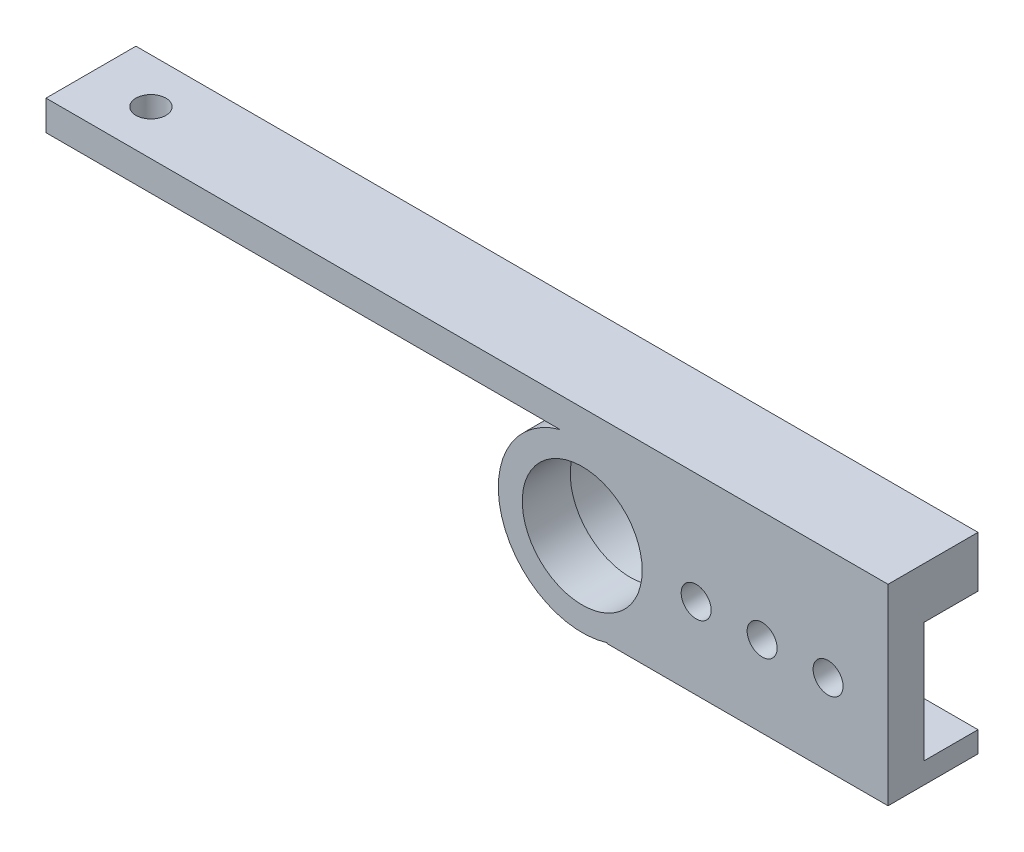
SolidWorks part; units mm, degrees
ref_plane "前视基准面" through (0, 0, 0) normal (0, 0, 1) x (1, 0, 0)
ref_plane "上视基准面" through (0, 0, 0) normal (0, 1, 0) x (1, 0, 0)
ref_plane "右视基准面" through (0, 0, 0) normal (1, 0, 0) x (0, 0, -1)
sketch "草图1" plane through (0, 0, 0) normal (0, 0, 1) x (1, 0, 0)
  line L1 (20, -10) -> (-20, -10)
  line L2 (20, -10) -> (20, 10)
  line L3 (20, 10) -> (-20, 10)
  line L4 (-20, -10) -> (-20, 10)
  line L5 (20, -10) -> (-20, 10) construction
  line L6 (20, 10) -> (-20, -10) construction
  point P0 (0, 0)
  dimension "D1" = 40
  dimension "D2" = 20
extrude "凸台-拉伸1" add sketch "草图1" along normal blind 6
sketch "草图2" plane through (0, 0, 6) normal (0, 0, 1) x (1, 0, 0)
  line L0 (20, -10) -> (20, 10) construction
  circle A0 centre (10, 0) radius 2.5
  circle A1 centre (-1, 0) radius 2.5
  circle A2 centre (-12, 0) radius 2.5
  dimension "D1" = 10
  dimension "D2" = 5
  dimension "D3" = 3
extrude "切除-拉伸1" cut sketch "草图2" against normal through all
sketch "草图3" plane through (0, 0, 6) normal (0, 0, 1) x (1, 0, 0)
  line L0 (20, 13.5) -> (20, 10)
  line L1 (20, -13.5) -> (-26.894, -13.5)
  line L3 (20, 13.5) -> (-26.894, 13.5)
  line L4 (-20, 10) -> (-20, -10)
  line L5 (-20, -10) -> (20, -10)
  line L6 (20, -10) -> (20, 10)
  line L7 (20, 10) -> (-20, 10)
  line L8 (-20, 10) -> (-20, -10)
  line L9 (-20, -10) -> (20, -10)
  line L10 (20, -10) -> (20, 10)
  line L11 (20, 10) -> (-20, 10)
  line L12 (-26.894, -13.5) -> (-26.894, 13.5)
  line L13 (20, -10.0394) -> (-26.894, 13.5) construction
  line L14 (20, 10.0394) -> (-26.894, -13.5) construction
  line L15 (20, -10) -> (20, -13.5)
  circle A0 centre (-31, 0) radius 11
  circle A1 centre (-31, 0) radius 14
  point P2 (0, 0)
  line M10 (-20, 10) -> (-20, -10)
  line M11 (-20, -10) -> (20, -10)
  line M13 (20, 10) -> (-20, 10)
  dimension "D3" = 22
  dimension "D4" = 28
  dimension "D2" = 3.5
  dimension "D1" = 0
extrude "凸台-拉伸2" add sketch "草图3" against normal blind 15 contours L3 A1 L1 L12 A0 | A1 L1 L15 M11 M10 | L1 A1 L8 A0 L12 | L8 A1 L3 L12 A0 | L8 A1 | A1 L0 L3 M10 M13 region at (-1.9449, 11.7771, 6) region at (-1.9449, -11.7771, 6) region at (-23.0173, 9.0328, 6) region at (-27.2274, 11.7946, 6) region at (-18.7882, 0, 6) region at (-23.0173, -9.0328, 6)
sketch "草图5" plane through (0, 0, 6) normal (0, 0, 1) x (1, 0, 0)
  circle A0 centre (-31, 0) radius 10
  circle A1 centre (-31, 0) radius 11 construction
  circle A2 centre (-31, 0) radius 11
  dimension "D1" = 20
extrude "凸台-拉伸3" add sketch "草图5" against normal blind 8
sketch "草图6" plane through (0, 0, 6) normal (0, 0, 1) x (1, 0, 0)
  circle A0 centre (-31, 0) radius 8.5
  circle A1 centre (-31, 0) radius 10 construction
  circle A2 centre (-31, 0) radius 10
  dimension "D1" = 17
sketch "草图7" plane through (0, 13.5, 0) normal (0, 1, 0) x (1, 0, 0)
  circle A0 centre (-16.8213, 3.0525) radius 3.3366
sketch "草图8" plane through (20, 0, 0) normal (1, 0, 0) x (0, 0, -1)
  line L1 (-6, 13.5) -> (9, 13.5)
  line L2 (-6, 13.5) -> (-6, 18.5)
  line L3 (-6, 18.5) -> (9, 18.5)
  line L4 (9, 13.5) -> (9, 18.5)
  dimension "D1" = 5
extrude "凸台-拉伸4" add sketch "草图8" against normal blind 200
sketch "草图9" plane through (0, 0, 6) normal (0, 0, 1) x (1, 0, 0)
  line L1 (-29.5663, 15.6648) -> (-25.1627, 15.6648)
  line L2 (-29.5663, 15.6648) -> (-29.5663, 11.9284)
  line L3 (-29.5663, 11.9284) -> (-25.1627, 11.9284)
  line L4 (-25.1627, 15.6648) -> (-25.1627, 11.9284)
extrude "凸台-拉伸5" add sketch "草图9" against normal through all
sketch "草图11" plane through (0, 18.5, 0) normal (0, 1, 0) x (1, 0, 0)
  line L0 (-120.4266, -6) -> (-120.4266, 9)
  line L1 (-180, -6) -> (20, -6) construction
  line L2 (-120.4266, 245.09) -> (-120.4266, -124.91) construction
  line L3 (-180, 9) -> (20, 9) construction
sketch "草图13" plane through (0, 18.5, 0) normal (0, 1, 0) x (1, 0, 0)
  line L1 (-120.4266, -6) -> (-183.1111, -6)
  line L2 (-120.4266, -6) -> (-120.4266, 12.5245)
  line L3 (-120.4266, 12.5245) -> (-183.1111, 12.5245)
  line L4 (-183.1111, -6) -> (-183.1111, 12.5245)
extrude "切除-拉伸2" cut sketch "草图13" against normal through all
sketch "草图14" plane through (0, 18.5, 0) normal (0, 1, 0) x (1, 0, 0)
  line L0 (-120.4266, 1.5) -> (-110.4266, 1.5) construction
  line L1 (-120.4266, -6) -> (-120.4266, 9) construction
  circle A0 centre (-110.4266, 1.5) radius 2.5
  dimension "D1" = 5
  dimension "D2" = 10
extrude "切除-拉伸3" cut sketch "草图14" against normal through all
